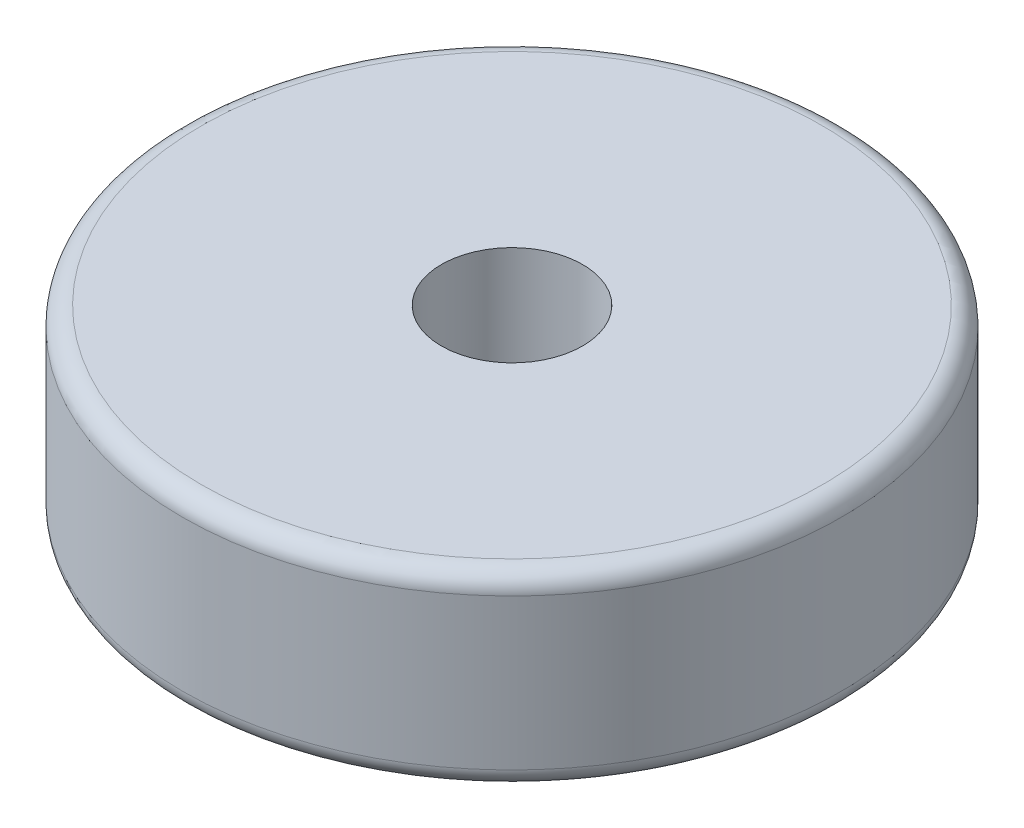
SolidWorks part; units mm, degrees
ref_plane "Front Plane" through (0, 0, 0) normal (0, 0, 1) x (1, 0, 0)
ref_plane "Top Plane" through (0, 0, 0) normal (0, 1, 0) x (1, 0, 0)
ref_plane "Right Plane" through (0, 0, 0) normal (1, 0, 0) x (0, 0, -1)
sketch "Sketch1" plane through (0, 0, 0) normal (0, 1, 0) x (1, 0, 0)
  circle A0 centre (0, 0) radius 44.45
  circle A2 centre (0, 0) radius 9.525
  dimension "D1" = 88.9
  dimension "D2" = 19.05
extrude "Boss-Extrude1" add sketch "Sketch1" along normal blind 25.4
fillet "Fillet1" radius 2.54 2 edges at (0, 0, 44.45) (0, 25.4, 44.45)
